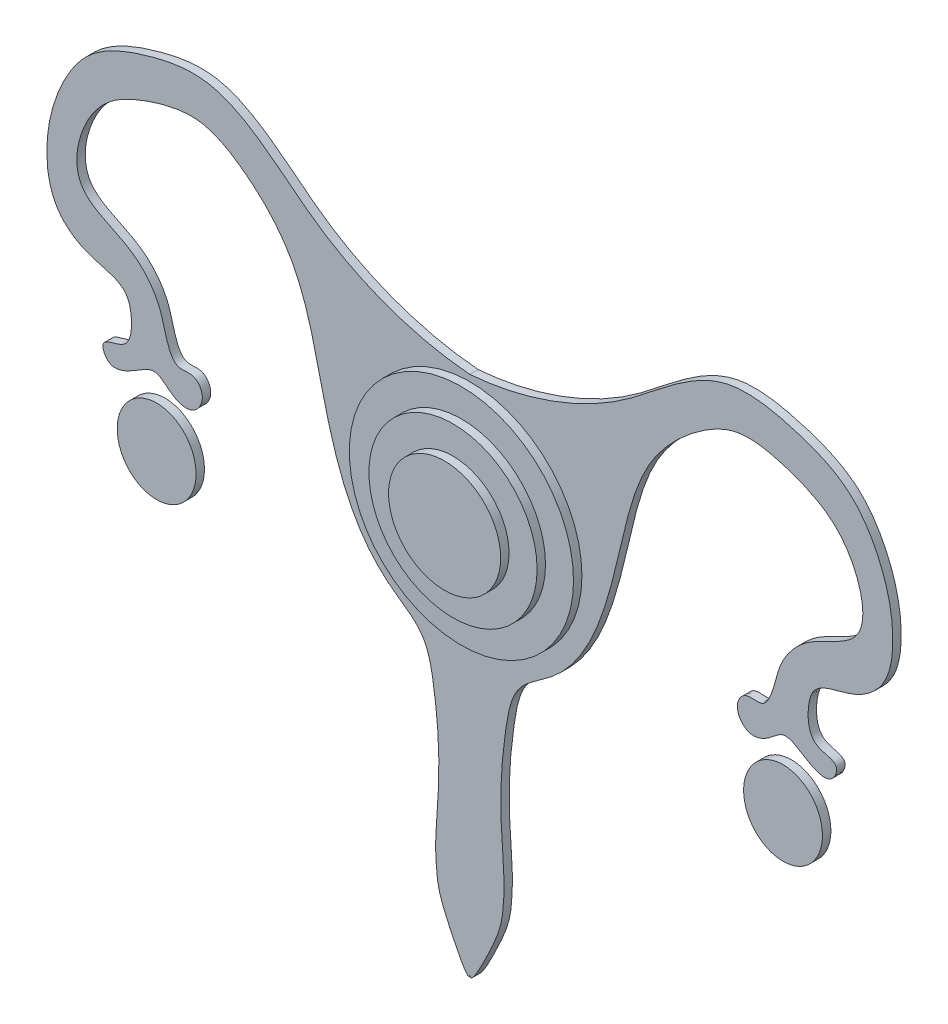
SolidWorks part; units mm, degrees
ref_plane "Front Plane" through (0, 0, 0) normal (0, 0, 1) x (1, 0, 0)
ref_plane "Top Plane" through (0, 0, 0) normal (0, 1, 0) x (1, 0, 0)
ref_plane "Right Plane" through (0, 0, 0) normal (1, 0, 0) x (0, 0, -1)
sketch "Sketch3" plane through (0, 0, 0) normal (0, 0, 1) x (1, 0, 0)
  line L0 (0, 94.186) -> (0, -105.814) construction
  ellipse E0 centre (111.7505, 14.5516) end of major axis (111.7505, 29.4895) minor radius 14.0603
  ellipse E1 centre (-111.7505, 14.5516) end of major axis (-111.7505, 29.4895) minor radius 14.0603
  spline S0 degree 3 poles (0, 94.186) (19.6537, 95.7873) (47.1668, 105.6436) (72.728, 128.3051) (92.9059, 140.0214) (115.6867, 135.7842) (136.2637, 127.4892) (147.6923, 108.7366) (152.077, 90.5104) (149.5025, 71.9443) (136.9842, 62.1727) (122.4735, 61.1173) (120.2279, 50.271) (121.156, 42.7622) (126.3642, 40.262) (132.2194, 39.537) (129.046, 31.5888) (120.1175, 34.3394) (112.7142, 41.2014) (106.5464, 34.3749) (98.9217, 31.7046) (93.8889, 39.0951) (98.1549, 45.5687) (104.9486, 43.2293) (108.7323, 51.3673) (110.2201, 61.0402) (118.5321, 71.5528) (129.4452, 76.0903) (142.5559, 83.7449) (139.0722, 102.6651) (128.3737, 115.8339) (113.0775, 122.2427) (96.3518, 126.2892) (78.4445, 116.2621) (60.2596, 97.5592) (52.082, 58.7785) (42.0469, 21.4241) (15.465, 6.7083) (12.3936, -10.4516) (10.6795, -27.4071) (11.3436, -44.0628) (12.4098, -55.7526) (11.7574, -68.7935) (10.2565, -74.8228) (-0.0016, -94.7938) (0, -91.1013) knots 0 0 0 0 0.087071 0.121466 0.151137 0.184673 0.218739 0.245122 0.27702 0.30084 0.32176 0.343171 0.354061 0.366931 0.371453 0.379445 0.386303 0.397454 0.413099 0.422542 0.433062 0.443806 0.451901 0.459842 0.469074 0.48428 0.50555 0.522539 0.537148 0.567114 0.589198 0.611438 0.638728 0.660449 0.697728 0.749749 0.832703 0.852973 0.875034 0.903781 0.92951 0.947165 0.956295 0.983817 1 1 1 1
  spline S1 degree 3 poles (0, 94.186) (-19.6537, 95.7873) (-47.1668, 105.6436) (-72.728, 128.3051) (-92.9059, 140.0214) (-115.6867, 135.7842) (-136.2637, 127.4892) (-147.6923, 108.7366) (-152.077, 90.5104) (-149.5025, 71.9443) (-136.9842, 62.1727) (-122.4735, 61.1173) (-120.2279, 50.271) (-121.156, 42.7622) (-126.3642, 40.262) (-132.2194, 39.537) (-129.046, 31.5888) (-120.1175, 34.3394) (-112.7142, 41.2014) (-106.5464, 34.3749) (-98.9217, 31.7046) (-93.8889, 39.0951) (-98.1549, 45.5687) (-104.9486, 43.2293) (-108.7323, 51.3673) (-110.2201, 61.0402) (-118.5321, 71.5528) (-129.4452, 76.0903) (-142.5559, 83.7449) (-139.0722, 102.6651) (-128.3737, 115.8339) (-113.0775, 122.2427) (-96.3518, 126.2892) (-78.4445, 116.2621) (-60.2596, 97.5592) (-52.082, 58.7785) (-42.0469, 21.4241) (-15.465, 6.7083) (-12.3936, -10.4516) (-10.6795, -27.4071) (-11.3436, -44.0628) (-12.4098, -55.7526) (-11.7574, -68.7935) (-10.2565, -74.8228) (0.0016, -94.7938) (0, -91.1013) knots 0 0 0 0 0.087071 0.121466 0.151137 0.184673 0.218739 0.245122 0.27702 0.30084 0.32176 0.343171 0.354061 0.366931 0.371453 0.379445 0.386303 0.397454 0.413099 0.422542 0.433062 0.443806 0.451901 0.459842 0.469074 0.48428 0.50555 0.522539 0.537148 0.567114 0.589198 0.611438 0.638728 0.660449 0.697728 0.749749 0.832703 0.852973 0.875034 0.903781 0.92951 0.947165 0.956295 0.983817 1 1 1 1
extrude "Boss-Extrude2" add sketch "Sketch3" against normal blind 3
sketch "Sketch4" plane through (0, 0, 0) normal (0, 0, 1) x (1, 0, 0)
  circle A0 centre (0, 51.957) radius 40
  dimension "D1" = 80
extrude "Boss-Extrude3" add sketch "Sketch4" along normal blind 3
sketch "Sketch5" plane through (0, 0, 3) normal (0, 0, 1) x (1, 0, 0)
  circle A0 centre (0, 51.957) radius 30
  dimension "D1" = 60
extrude "Boss-Extrude4" add sketch "Sketch5" along normal blind 3
sketch "Sketch6" plane through (0, 0, 6) normal (0, 0, 1) x (1, 0, 0)
  circle A0 centre (0, 51.957) radius 20
  dimension "D1" = 40
extrude "Boss-Extrude5" add sketch "Sketch6" along normal blind 3
